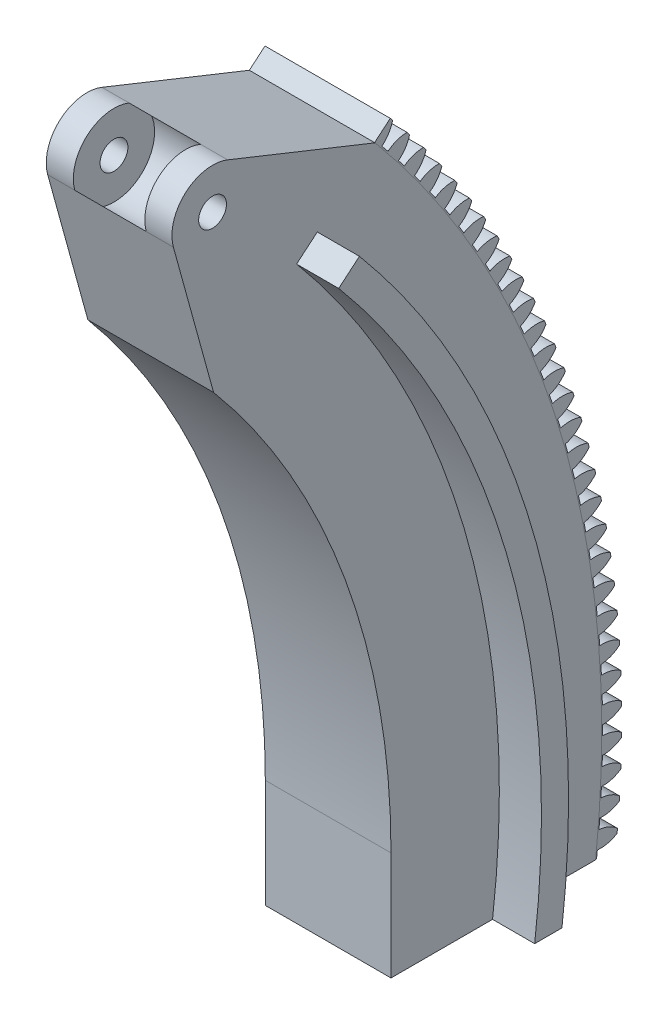
SolidWorks part; units mm, degrees
material "ABS"
ref_plane "Front Plane" through (0, 0, 0) normal (0, 0, 1) x (1, 0, 0)
ref_plane "Top Plane" through (0, 0, 0) normal (0, 1, 0) x (1, 0, 0)
ref_plane "Right Plane" through (0, 0, 0) normal (1, 0, 0) x (0, 0, -1)
ref_plane "Plane2" through (6.35, 0, 0) normal (1, 0, 0) x (0, 0, -1)
sketch "Sketch1" plane through (0, 0, 0) normal (1, 0, 0) x (0, 0, -1)
  line L0 (-1000, 0) -> (177.8, 0) construction
  line L1 (177.8, 0) -> (177.8, -25.4)
  line L2 (0, 0) -> (136.2027, 114.2876) construction
  line L4 (227.2, 0) -> (49000, 0) construction
  line L7 (177.8, -25.4) -> (227.2, -25.4) construction
  line L8 (227.2, 0) -> (227.2, -25.4) construction
  line L10 (-1.0719, -0.8495) -> (179.1555, 141.9904) construction
  line L61 (181.0098, 139.6187) -> (0, 0) construction
  line L62 (136.2027, 114.2876) -> (126.7844, 148.4774)
  line L64 (177.8, -25.4) -> (225.7757, -25.4)
  line L65 (136.2027, 114.2876) -> (155.124, 130.1645) construction
  line L66 (155.124, 130.1645) -> (174.0453, 146.0413) construction
  line L68 (0, 0) -> (35966.99, 34732.9185) construction
  line L69 (178.0587, 141.1212) -> (178.0836, 141.1409) construction
  line L70 (0, 0) -> (135.9673, 151.007) construction
  line L71 (139.5033, 159.8514) -> (174.0453, 146.0413)
  arc A2 (177.8, 0) -> (136.2027, 114.2876) centre (0, 0) ccw
  circle A19 centre (0, 0) radius 228.6 construction
  arc A22 (174.0453, 146.0413) -> (227.2, 0) centre (0, 0) cw
  arc A23 (227.2, 0) -> (225.7757, -25.4) centre (0, 0) cw
  arc A24 (126.7844, 148.4774) -> (139.5033, 159.8514) centre (135.9673, 151.007) cw
  point P6 (178.0836, 141.1409)
  point P7 (136.2027, 114.2876)
  dimension "D1" = 177.8
  dimension "D2" = 6.35
  dimension "D12" = 457.2
  dimension "D8" = 9.525
  dimension "D3" = 40
  dimension "D4" = 49.4
  dimension "D5" = 25.4
  dimension "D6" = 203.2
  dimension "D7" = 48
  dimension "D13" = 44
sketch "Sketch2" plane through (6.35, 0, 0) normal (1, 0, 0) x (0, 0, -1)
  line L0 (0, 0) -> (165.1, 0) construction
  line L1 (165.1, 0) -> (190.5, 0) construction
  line L2 (0, 0) -> (49240.3877, 8682.4089) construction
  circle A0 centre (165.1, 0) radius 3.2639
  circle A1 centre (190.5, 0) radius 3.2639
  arc A3 (165.1, 0) -> (162.5918, 28.6693) centre (0, 0) ccw construction
  circle A4 centre (162.5918, 28.6693) radius 3.2639
  arc A5 (190.5, 0) -> (187.6059, 33.08) centre (0, 0) ccw construction
  circle A6 centre (187.6059, 33.08) radius 3.2639
  dimension "D3" = 6.5278
  dimension "D4" = 6.5278
  dimension "D6" = 6.5278
  dimension "D7" = 6.5278
  dimension "D1" = 165.1
  dimension "D2" = 25.4
  dimension "D5" = 10
sketch "Sketch11" plane through (6.35, 0, 0) normal (1, 0, 0) x (0, 0, -1)
  line L0 (-785.502, -659.1144) -> (0, 0) construction
  line L2 (-1000, 0) -> (0, 0) construction
  line L4 (155.6602, 130.6144) -> (177.7223, 149.1267)
  line L5 (177.7223, 149.1267) -> (921.7047, 773.4021) construction
  line L6 (232, 0) -> (232, -25.4) construction
  line L7 (232, -25.4) -> (222.9391, -25.4) construction
  line L8 (201.6062, -25.4) -> (230.6054, -25.4)
  line L9 (203.2, 0) -> (232, 0) construction
  arc A0 (-230, 0) -> (-176.1902, -147.8412) centre (0, 0) ccw construction
  arc A1 (-232, 0) -> (-177.7223, -149.1267) centre (0, 0) ccw construction
  arc A2 (-229.6, 0) -> (-175.8838, -147.584) centre (0, 0) ccw construction
  arc A3 (232, 0) -> (177.7223, 149.1267) centre (0, 0) ccw
  arc A4 (230, 0) -> (176.1902, 147.8412) centre (0, 0) ccw construction
  arc A5 (-229.6, 0) -> (-175.8838, -147.584) centre (0, 0) ccw
  arc A6 (155.6602, 130.6144) -> (203.2, 0) centre (0, 0) cw
  arc A7 (232, 0) -> (230.6054, -25.4) centre (0, 0) cw
  arc A8 (203.2, 0) -> (201.6062, -25.4) centre (0, 0) cw
  dimension "D1" = 460
  dimension "D2" = 464
  dimension "D4" = 203.2
  dimension "D3" = 2.4
  dimension "D6" = 25.4
extrude "Boss-Extrude2" add sketch "Sketch11" against normal blind 6.35 contours A3 L4 region at (6.35, 60.7212, -203.0048)
sketch "Sketch12" plane through (6.35, 0, 0) normal (1, 0, 0) x (0, 0, -1)
  line L0 (0, 0) -> (232, 0) construction
  line L2 (229.9946, 1.5708) -> (229.9946, -1.5708) construction
  line L3 (0, 0) -> (227.4972, 1.1241) construction
  line L4 (225.6789, 0) -> (232.9848, 2.6591) construction
  line L5 (0, 0) -> (232.9783, 3.1825) construction
  line L6 (229.9946, 1.5708) -> (229.9517, 4.7121) construction
  circle A0 centre (0, 0) radius 230 construction
  arc A1 (230.6054, -25.4) -> (177.7223, 149.1267) centre (0, 0) ccw construction
  circle A2 centre (0, 0) radius 227.5 construction
  arc A3 (227.4972, 1.1241) -> (232.9725, 3.5819) centre (227.4606, 8.5329) ccw
  arc A4 (231.5994, -25.5095) -> (232.9725, -3.5819) centre (0, 0) cw construction
  arc A5 (227.4972, -1.1241) -> (232.9725, -3.5819) centre (227.4606, -8.5329) cw
  arc A6 (231.5994, -25.5095) -> (178.4884, 149.7695) centre (0, 0) ccw
  arc A7 (231.5994, -25.5095) -> (232.9725, 3.5819) centre (0, 0) ccw construction
  arc A8 (227.4972, 1.1241) -> (227.4972, -1.1241) centre (0, 0) cw
  arc A9 (230.6054, -25.4) -> (177.7223, 149.1267) centre (0, 0) ccw construction
  arc A10 (232.9725, 3.5819) -> (232.9725, -3.5819) centre (0, 0) cw
  dimension "D1" = 460
  dimension "D3" = 20
  dimension "D4" = 0.783
  dimension "D5" = 4.5
  dimension "D2" = 1
extrude "Boss-Extrude3" add sketch "Sketch1" along normal blind 29.464
extrude "Cut-Extrude4" cut sketch "Sketch12" against normal blind 6.35
pattern_circular "CirPattern3" count 230 every 1.565 about axis through (0, 0, 0) along (1, 0, 0) of "Cut-Extrude4"
sketch "Sketch15" plane through (6.35, 0, 0) normal (1, 0, 0) x (0, 0, -1)
  line L0 (0, 0) -> (135.9673, 151.007) construction
  line L2 (0, 0) -> (102.4673, 0) construction
  circle A0 centre (135.9673, 151.007) radius 3.2639
  dimension "D3" = 6.5278
  dimension "D1" = 203.2
  dimension "D2" = 48
extrude "Cut-Extrude7" cut sketch "Sketch15" against normal through all both and the other way through all
sketch "Sketch22" plane through (6.35, 0, 0) normal (1, 0, 0) x (0, 0, -1)
  line L0 (0, 0) -> (135.9673, 151.007)
  line L1 (0, 0) -> (177.8, 0)
  dimension "D1" = 177.8
sketch "Sketch23" plane through (0, 0, 0) normal (1, 0, 0) x (0, 0, -1)
  line L0 (0, 0) -> (177.8, 0) construction
  line L1 (0, 0) -> (136.2027, 114.2876) construction
  line L2 (177.8, 0) -> (196.85, 0) construction
  line L3 (136.2027, 114.2876) -> (155.6602, 130.6144) construction
  line L5 (155.6602, 130.6144) -> (160.5246, 134.6961)
  line L7 (201.6062, -25.4) -> (0, 0) construction
  line L8 (208.0049, -25.4) -> (201.6062, -25.4)
  line L9 (177.8, -25.4) -> (226.0776, -25.4) construction
  arc A0 (177.8, 0) -> (136.2027, 114.2876) centre (0, 0) ccw construction
  circle A2 centre (196.85, 0) radius 6.35 construction
  arc A3 (203.2, 0) -> (155.6602, 130.6144) centre (0, 0) ccw
  arc A4 (209.55, 0) -> (160.5246, 134.6961) centre (0, 0) ccw
  circle A5 centre (215.9, 0) radius 6.35 construction
  arc A6 (203.2, 0) -> (201.6062, -25.4) centre (0, 0) cw
  arc A7 (209.55, 0) -> (208.0049, -25.4) centre (0, 0) cw
  dimension "D4" = 6.35
  dimension "D5" = 12.7
  dimension "D6" = 12.7
  dimension "D1" = 177.8
  dimension "D2" = 40
  dimension "D3" = 19.05
extrude "Boss-Extrude4" add sketch "Sketch23" against normal blind 9.8742
ref_plane "Plane3" through (14.732, 0, 0) normal (1, 0, 0) x (0, 0, -1)
mirror "Mirror2" about plane through (14.732, 0, 0) normal (1, 0, 0) of "Boss-Extrude4"
sketch "Sketch27" plane through (6.35, 0, 0) normal (1, 0, 0) x (0, 0, -1)
  line L2 (177.7223, 149.1267) -> (174.0453, 146.0413)
  line L3 (177.7223, 149.1267) -> (174.0453, 146.0413)
  line L7 (225.7757, -25.4) -> (226.0776, -25.4)
  line L8 (225.7757, -25.4) -> (226.0776, -25.4)
  arc A4 (227.2191, 11.3011) -> (227.0964, 13.5458) centre (0, 0) ccw
  arc A95 (231.8253, 9.0012) -> (231.7841, 10.0069) centre (0, 0) ccw
  arc A111 (227.3816, 7.3377) -> (231.8253, 9.0012) centre (227.1427, 14.7428) ccw
  arc A112 (227.3816, 7.3377) -> (231.8253, 9.0012) centre (227.1427, 14.7428) ccw
  arc A113 (231.7841, 10.0069) -> (227.2191, 11.3011) centre (227.5872, 3.9012) ccw
  arc A114 (231.7841, 10.0069) -> (227.2191, 11.3011) centre (227.5872, 3.9012) ccw
  arc A139 (227.2191, 11.3011) -> (227.0964, 13.5458) centre (0, 0) ccw
  arc A141 (227.0964, 13.5458) -> (231.493, 15.3301) centre (226.6552, 20.9417) ccw
  arc A143 (227.0964, 13.5458) -> (231.493, 15.3301) centre (226.6552, 20.9417) ccw
  arc A145 (231.493, 15.3301) -> (231.4243, 16.3343) centre (0, 0) ccw
  arc A147 (231.493, 15.3301) -> (231.4243, 16.3343) centre (0, 0) ccw
  arc A149 (231.4243, 16.3343) -> (226.8257, 17.5033) centre (227.3957, 10.1163) ccw
  arc A151 (231.4243, 16.3343) -> (226.8257, 17.5033) centre (227.3957, 10.1163) ccw
  arc A153 (226.8257, 17.5033) -> (226.6416, 19.7439) centre (0, 0) ccw
  arc A155 (226.8257, 17.5033) -> (226.6416, 19.7439) centre (0, 0) ccw
  arc A157 (226.6416, 19.7439) -> (230.9878, 21.6476) centre (225.9986, 27.1249) ccw
  arc A159 (226.6416, 19.7439) -> (230.9878, 21.6476) centre (225.9986, 27.1249) ccw
  arc A161 (230.9878, 21.6476) -> (230.8918, 22.6495) centre (0, 0) ccw
  arc A163 (230.9878, 21.6476) -> (230.8918, 22.6495) centre (0, 0) ccw
  arc A165 (230.8918, 22.6495) -> (226.2629, 23.6925) centre (227.0345, 16.3238) ccw
  arc A167 (230.8918, 22.6495) -> (226.2629, 23.6925) centre (227.0345, 16.3238) ccw
  arc A169 (226.2629, 23.6925) -> (226.0178, 25.9272) centre (0, 0) ccw
  arc A171 (226.2629, 23.6925) -> (226.0178, 25.9272) centre (0, 0) ccw
  arc A173 (226.0178, 25.9272) -> (230.3104, 27.9489) centre (225.1734, 33.2879) ccw
  arc A175 (226.0178, 25.9272) -> (230.3104, 27.9489) centre (225.1734, 33.2879) ccw
  arc A177 (230.3104, 27.9489) -> (230.1869, 28.9478) centre (0, 0) ccw
  arc A179 (230.3104, 27.9489) -> (230.1869, 28.9478) centre (0, 0) ccw
  arc A181 (230.1869, 28.9478) -> (225.5314, 29.8639) centre (226.5039, 22.5191) ccw
  arc A182 (230.1869, 28.9478) -> (225.5314, 29.8639) centre (226.5039, 22.5191) ccw
  arc A184 (225.5314, 29.8639) -> (225.2252, 32.0911) centre (0, 0) ccw
  arc A186 (225.5314, 29.8639) -> (225.2252, 32.0911) centre (0, 0) ccw
  arc A189 (231.8253, 9.0012) -> (231.7841, 10.0069) centre (0, 0) ccw
  arc A282 (225.2252, 32.0911) -> (229.461, 34.2294) centre (224.1801, 39.426) ccw
  arc A284 (225.2252, 32.0911) -> (229.461, 34.2294) centre (224.1801, 39.426) ccw
  arc A286 (229.461, 34.2294) -> (229.3104, 35.2245) centre (0, 0) ccw
  arc A288 (229.461, 34.2294) -> (229.3104, 35.2245) centre (0, 0) ccw
  arc A290 (229.3104, 35.2245) -> (224.6315, 36.0131) centre (225.8043, 28.6976) ccw
  arc A292 (229.3104, 35.2245) -> (224.6315, 36.0131) centre (225.8043, 28.6976) ccw
  arc A294 (224.6315, 36.0131) -> (224.2647, 38.2311) centre (0, 0) ccw
  arc A296 (224.6315, 36.0131) -> (224.2647, 38.2311) centre (0, 0) ccw
  arc A298 (224.2647, 38.2311) -> (228.4404, 40.4843) centre (223.0196, 45.5347) ccw
  arc A300 (224.2647, 38.2311) -> (228.4404, 40.4843) centre (223.0196, 45.5347) ccw
  arc A302 (228.4404, 40.4843) -> (228.2626, 41.4749) centre (0, 0) ccw
  arc A304 (228.4404, 40.4843) -> (228.2626, 41.4749) centre (0, 0) ccw
  arc A306 (228.2626, 41.4749) -> (223.564, 42.1355) centre (224.9362, 34.8547) ccw
  arc A308 (228.2626, 41.4749) -> (223.564, 42.1355) centre (224.9362, 34.8547) ccw
  arc A310 (223.564, 42.1355) -> (223.1367, 44.3426) centre (0, 0) ccw
  arc A312 (223.564, 42.1355) -> (223.1367, 44.3426) centre (0, 0) ccw
  arc A314 (223.1367, 44.3426) -> (227.2494, 46.709) centre (221.6926, 51.6095) ccw
  arc A316 (223.1367, 44.3426) -> (227.2494, 46.709) centre (221.6926, 51.6095) ccw
  arc A318 (227.2494, 46.709) -> (227.0446, 47.6944) centre (0, 0) ccw
  arc A320 (227.2494, 46.709) -> (227.0446, 47.6944) centre (0, 0) ccw
  arc A322 (227.0446, 47.6944) -> (222.3296, 48.2264) centre (223.9002, 40.9858) ccw
  arc A324 (227.0446, 47.6944) -> (222.3296, 48.2264) centre (223.9002, 40.9858) ccw
  arc A326 (222.3296, 48.2264) -> (221.8422, 50.421) centre (0, 0) ccw
  arc A328 (222.3296, 48.2264) -> (221.8422, 50.421) centre (0, 0) ccw
  arc A330 (221.8422, 50.421) -> (225.8887, 52.8988) centre (220.2002, 57.6457) ccw
  arc A332 (221.8422, 50.421) -> (225.8887, 52.8988) centre (220.2002, 57.6457) ccw
  arc A334 (225.8887, 52.8988) -> (225.6571, 53.8783) centre (0, 0) ccw
  arc A336 (225.8887, 52.8988) -> (225.6571, 53.8783) centre (0, 0) ccw
  arc A338 (225.6571, 53.8783) -> (220.9294, 54.2813) centre (222.6972, 47.0863) ccw
  arc A340 (225.6571, 53.8783) -> (220.9294, 54.2813) centre (222.6972, 47.0863) ccw
  arc A342 (220.9294, 54.2813) -> (220.3822, 56.4618) centre (0, 0) ccw
  arc A344 (220.9294, 54.2813) -> (220.3822, 56.4618) centre (0, 0) ccw
  arc A346 (220.3822, 56.4618) -> (224.3595, 59.0492) centre (218.5434, 63.6389) ccw
  arc A348 (220.3822, 56.4618) -> (224.3595, 59.0492) centre (218.5434, 63.6389) ccw
  arc A350 (224.3595, 59.0492) -> (224.1012, 60.022) centre (0, 0) ccw
  arc A352 (224.3595, 59.0492) -> (224.1012, 60.022) centre (0, 0) ccw
  arc A354 (224.1012, 60.022) -> (219.3643, 60.2956) centre (221.3279, 53.1516) ccw
  arc A356 (224.1012, 60.022) -> (219.3643, 60.2956) centre (221.3279, 53.1516) ccw
  arc A358 (219.3643, 60.2956) -> (218.7577, 62.4604) centre (0, 0) ccw
  arc A360 (219.3643, 60.2956) -> (218.7577, 62.4604) centre (0, 0) ccw
  arc A362 (218.7577, 62.4604) -> (222.6629, 65.1555) centre (216.7236, 69.5847) ccw
  arc A364 (218.7577, 62.4604) -> (222.6629, 65.1555) centre (216.7236, 69.5847) ccw
  arc A366 (222.6629, 65.1555) -> (222.3781, 66.1209) centre (0, 0) ccw
  arc A368 (222.6629, 65.1555) -> (222.3781, 66.1209) centre (0, 0) ccw
  arc A370 (222.3781, 66.1209) -> (217.6355, 66.265) centre (219.7935, 59.1773) ccw
  arc A372 (222.3781, 66.1209) -> (217.6355, 66.265) centre (219.7935, 59.1773) ccw
  arc A374 (217.6355, 66.265) -> (216.97, 68.4124) centre (0, 0) ccw
  arc A376 (217.6355, 66.265) -> (216.97, 68.4124) centre (0, 0) ccw
  arc A378 (216.97, 68.4124) -> (220.8001, 71.2132) centre (214.742, 75.4785) ccw
  arc A380 (216.97, 68.4124) -> (220.8001, 71.2132) centre (214.742, 75.4785) ccw
  arc A382 (220.8001, 71.2132) -> (220.4891, 72.1704) centre (0, 0) ccw
  arc A384 (220.8001, 71.2132) -> (220.4891, 72.1704) centre (0, 0) ccw
  arc A386 (220.4891, 72.1704) -> (215.7443, 72.185) centre (218.0951, 65.1589) ccw
  arc A388 (220.4891, 72.1704) -> (215.7443, 72.185) centre (218.0951, 65.1589) ccw
  arc A390 (215.7443, 72.185) -> (215.0204, 74.3134) centre (0, 0) ccw
  arc A394 (215.7443, 72.185) -> (215.0204, 74.3134) centre (0, 0) ccw
  arc A398 (215.0204, 74.3134) -> (218.7726, 77.2177) centre (212.6002, 81.3159) ccw
  arc A402 (215.0204, 74.3134) -> (218.7726, 77.2177) centre (212.6002, 81.3159) ccw
  arc A406 (218.7726, 77.2177) -> (218.4355, 78.1661) centre (0, 0) ccw
  arc A410 (218.7726, 77.2177) -> (218.4355, 78.1661) centre (0, 0) ccw
  arc A414 (218.4355, 78.1661) -> (213.692, 78.0511) centre (216.2339, 71.0918) ccw
  arc A418 (218.4355, 78.1661) -> (213.692, 78.0511) centre (216.2339, 71.0918) ccw
  arc A420 (213.692, 78.0511) -> (212.9103, 80.1589) centre (0, 0) ccw
  arc A422 (213.692, 78.0511) -> (212.9103, 80.1589) centre (0, 0) ccw
  arc A423 (212.9103, 80.1589) -> (216.5817, 83.1646) centre (210.2998, 87.0927) ccw
  arc A424 (212.9103, 80.1589) -> (216.5817, 83.1646) centre (210.2998, 87.0927) ccw
  arc A425 (216.5817, 83.1646) -> (216.2189, 84.1034) centre (0, 0) ccw
  arc A426 (216.5817, 83.1646) -> (216.2189, 84.1034) centre (0, 0) ccw
  arc A427 (216.2189, 84.1034) -> (211.4804, 83.8589) centre (214.2114, 76.9716) ccw
  arc A428 (216.2189, 84.1034) -> (211.4804, 83.8589) centre (214.2114, 76.9716) ccw
  arc A429 (211.4804, 83.8589) -> (210.6414, 85.9446) centre (0, 0) ccw
  arc A430 (211.4804, 83.8589) -> (210.6414, 85.9446) centre (0, 0) ccw
  arc A431 (210.6414, 85.9446) -> (214.2293, 89.0495) centre (207.8424, 92.8045) ccw
  arc A432 (210.6414, 85.9446) -> (214.2293, 89.0495) centre (207.8424, 92.8045) ccw
  arc A434 (214.2293, 89.0495) -> (213.841, 89.978) centre (0, 0) ccw
  arc A436 (214.2293, 89.0495) -> (213.841, 89.978) centre (0, 0) ccw
  arc A438 (213.841, 89.978) -> (209.1109, 89.6041) centre (212.029, 82.794) ccw
  arc A440 (213.841, 89.978) -> (209.1109, 89.6041) centre (212.029, 82.794) ccw
  arc A442 (209.1109, 89.6041) -> (208.2152, 91.6661) centre (0, 0) ccw
  arc A444 (209.1109, 89.6041) -> (208.2152, 91.6661) centre (0, 0) ccw
  arc A446 (208.2152, 91.6661) -> (211.717, 94.8679) centre (205.2299, 98.4471) ccw
  arc A448 (208.2152, 91.6661) -> (211.717, 94.8679) centre (205.2299, 98.4471) ccw
  arc A450 (211.717, 94.8679) -> (211.3034, 95.7855) centre (0, 0) ccw
  arc A452 (211.717, 94.8679) -> (211.3034, 95.7855) centre (0, 0) ccw
  arc A454 (211.3034, 95.7855) -> (206.5853, 95.2825) centre (209.6884, 88.5547) ccw
  arc A456 (211.3034, 95.7855) -> (206.5853, 95.2825) centre (209.6884, 88.5547) ccw
  arc A458 (206.5853, 95.2825) -> (205.6337, 97.3193) centre (0, 0) ccw
  arc A460 (206.5853, 95.2825) -> (205.6337, 97.3193) centre (0, 0) ccw
  arc A462 (205.6337, 97.3193) -> (209.0467, 100.6155) centre (202.4643, 104.0162) ccw
  arc A464 (205.6337, 97.3193) -> (209.0467, 100.6155) centre (202.4643, 104.0162) ccw
  arc A466 (209.0467, 100.6155) -> (208.6082, 101.5215) centre (0, 0) ccw
  arc A467 (209.0467, 100.6155) -> (208.6082, 101.5215) centre (0, 0) ccw
  arc A468 (208.6082, 101.5215) -> (203.9056, 100.8898) centre (207.1913, 94.2492) ccw
  arc A469 (208.6082, 101.5215) -> (203.9056, 100.8898) centre (207.1913, 94.2492) ccw
  arc A470 (203.9056, 100.8898) -> (202.8987, 102.8998) centre (0, 0) ccw
  arc A471 (203.9056, 100.8898) -> (202.8987, 102.8998) centre (0, 0) ccw
  arc A472 (202.8987, 102.8998) -> (206.2204, 106.288) centre (199.5476, 109.5076) ccw
  arc A473 (202.8987, 102.8998) -> (206.2204, 106.288) centre (199.5476, 109.5076) ccw
  arc A474 (206.2204, 106.288) -> (205.7574, 107.1817) centre (0, 0) ccw
  arc A475 (206.2204, 106.288) -> (205.7574, 107.1817) centre (0, 0) ccw
  arc A476 (205.7574, 107.1817) -> (201.0737, 106.4218) centre (204.5396, 99.8735) ccw
  arc A477 (205.7574, 107.1817) -> (201.0737, 106.4218) centre (204.5396, 99.8735) ccw
  arc A478 (201.0737, 106.4218) -> (200.0123, 108.4036) centre (0, 0) ccw
  arc A479 (201.0737, 106.4218) -> (200.0123, 108.4036) centre (0, 0) ccw
  arc A480 (200.0123, 108.4036) -> (203.2402, 111.8812) centre (196.4819, 114.9174) ccw
  arc A481 (200.0123, 108.4036) -> (203.2402, 111.8812) centre (196.4819, 114.9174) ccw
  arc A482 (203.2402, 111.8812) -> (202.7529, 112.7619) centre (0, 0) ccw
  arc A483 (203.2402, 111.8812) -> (202.7529, 112.7619) centre (0, 0) ccw
  arc A484 (202.7529, 112.7619) -> (198.0918, 111.8744) centre (201.7352, 105.4232) ccw
  arc A485 (202.7529, 112.7619) -> (198.0918, 111.8744) centre (201.7352, 105.4232) ccw
  arc A486 (198.0918, 111.8744) -> (196.9766, 113.8264) centre (0, 0) ccw
  arc A487 (198.0918, 111.8744) -> (196.9766, 113.8264) centre (0, 0) ccw
  arc A488 (196.9766, 113.8264) -> (200.1084, 117.3909) centre (193.2697, 120.2413) ccw
  arc A489 (196.9766, 113.8264) -> (200.1084, 117.3909) centre (193.2697, 120.2413) ccw
  arc A490 (200.1084, 117.3909) -> (199.5972, 118.258) centre (0, 0) ccw
  arc A491 (200.1084, 117.3909) -> (199.5972, 118.258) centre (0, 0) ccw
  arc A492 (199.5972, 118.258) -> (194.9621, 117.2435) centre (198.7804, 110.8942) ccw
  arc A493 (199.5972, 118.258) -> (194.9621, 117.2435) centre (198.7804, 110.8942) ccw
  arc A494 (194.9621, 117.2435) -> (193.794, 119.1643) centre (0, 0) ccw
  arc A495 (194.9621, 117.2435) -> (193.794, 119.1643) centre (0, 0) ccw
  arc A496 (193.794, 119.1643) -> (196.8272, 122.8131) centre (189.9132, 125.4756) ccw
  arc A497 (193.794, 119.1643) -> (196.8272, 122.8131) centre (189.9132, 125.4756) ccw
  arc A498 (196.8272, 122.8131) -> (196.2926, 123.6658) centre (0, 0) ccw
  arc A499 (196.8272, 122.8131) -> (196.2926, 123.6658) centre (0, 0) ccw
  arc A500 (196.2926, 123.6658) -> (191.6869, 122.5251) centre (195.6771, 116.2824) ccw
  arc A501 (196.2926, 123.6658) -> (191.6869, 122.5251) centre (195.6771, 116.2824) ccw
  arc A502 (191.6869, 122.5251) -> (190.4667, 124.4133) centre (0, 0) ccw
  arc A503 (191.6869, 122.5251) -> (190.4667, 124.4133) centre (0, 0) ccw
  arc A504 (190.4667, 124.4133) -> (193.3992, 128.1435) centre (186.415, 130.6162) ccw
  arc A505 (190.4667, 124.4133) -> (193.3992, 128.1435) centre (186.415, 130.6162) ccw
  arc A506 (193.3992, 128.1435) -> (192.8414, 128.9814) centre (0, 0) ccw
  arc A507 (193.3992, 128.1435) -> (192.8414, 128.9814) centre (0, 0) ccw
  arc A508 (192.8414, 128.9814) -> (188.2686, 127.7153) centre (192.4279, 121.5839) ccw
  arc A509 (192.8414, 128.9814) -> (188.2686, 127.7153) centre (192.4279, 121.5839) ccw
  arc A510 (188.2686, 127.7153) -> (186.9974, 129.5694) centre (0, 0) ccw
  arc A511 (188.2686, 127.7153) -> (186.9974, 129.5694) centre (0, 0) ccw
  arc A512 (186.9974, 129.5694) -> (189.8268, 133.3784) centre (182.7777, 135.6594) ccw
  arc A513 (186.9974, 129.5694) -> (189.8268, 133.3784) centre (182.7777, 135.6594) ccw
  arc A514 (189.8268, 133.3784) -> (189.2464, 134.2007) centre (0, 0) ccw
  arc A515 (189.8268, 133.3784) -> (189.2464, 134.2007) centre (0, 0) ccw
  arc A516 (189.2464, 134.2007) -> (184.7098, 132.8101) centre (189.0351, 126.7947) ccw
  arc A517 (189.2464, 134.2007) -> (184.7098, 132.8101) centre (189.0351, 126.7947) ccw
  arc A518 (184.7098, 132.8101) -> (183.3884, 134.6289) centre (0, 0) ccw
  arc A519 (184.7098, 132.8101) -> (183.3884, 134.6289) centre (0, 0) ccw
  arc A520 (225.7757, -25.4) -> (174.0453, 146.0413) centre (0, 0) ccw
  arc A521 (225.7757, -25.4) -> (174.0453, 146.0413) centre (0, 0) ccw
  arc A522 (227.4972, -1.1241) -> (227.4972, 1.1241) centre (0, 0) ccw
  arc A523 (227.4972, -1.1241) -> (227.4972, 1.1241) centre (0, 0) ccw
  arc A524 (227.4972, 1.1241) -> (231.9847, 2.6656) centre (227.4606, 8.5329) ccw
  arc A525 (227.4972, 1.1241) -> (231.9847, 2.6656) centre (227.4606, 8.5329) ccw
  arc A526 (231.9847, 2.6656) -> (231.9709, 3.672) centre (0, 0) ccw
  arc A527 (231.9847, 2.6656) -> (231.9709, 3.672) centre (0, 0) ccw
  arc A528 (231.9709, 3.672) -> (227.4431, 5.0904) centre (227.6088, -2.3167) ccw
  arc A529 (231.9709, 3.672) -> (227.4431, 5.0904) centre (227.6088, -2.3167) ccw
  arc A530 (227.4431, 5.0904) -> (227.3816, 7.3377) centre (0, 0) ccw
  arc A531 (227.4431, 5.0904) -> (227.3816, 7.3377) centre (0, 0) ccw
  arc A532 (231.9709, -3.672) -> (231.9847, -2.6656) centre (0, 0) ccw
  arc A533 (231.9709, -3.672) -> (231.9847, -2.6656) centre (0, 0) ccw
  arc A534 (231.9847, -2.6656) -> (227.4972, -1.1241) centre (227.4606, -8.5329) ccw
  arc A535 (231.9847, -2.6656) -> (227.4972, -1.1241) centre (227.4606, -8.5329) ccw
  arc A536 (183.3884, 134.6289) -> (186.1128, 138.5137) centre (179.004, 140.6013) ccw
  arc A537 (183.3884, 134.6289) -> (186.1128, 138.5137) centre (179.004, 140.6013) ccw
  arc A538 (186.1128, 138.5137) -> (185.5101, 139.3198) centre (0, 0) ccw
  arc A539 (186.1128, 138.5137) -> (185.5101, 139.3198) centre (0, 0) ccw
  arc A540 (185.5101, 139.3198) -> (181.0132, 137.8059) centre (185.5011, 131.9108) ccw
  arc A541 (185.5101, 139.3198) -> (181.0132, 137.8059) centre (185.5011, 131.9108) ccw
  arc A542 (181.0132, 137.8059) -> (179.6426, 139.5879) centre (0, 0) ccw
  arc A543 (181.0132, 137.8059) -> (179.6426, 139.5879) centre (0, 0) ccw
  arc A544 (179.6426, 139.5879) -> (182.2598, 143.5456) centre (175.0967, 145.4383) ccw
  arc A545 (179.6426, 139.5879) -> (182.2598, 143.5456) centre (175.0967, 145.4383) ccw
  arc A546 (182.2598, 143.5456) -> (181.6354, 144.335) centre (0, 0) ccw
  arc A547 (182.2598, 143.5456) -> (181.6354, 144.335) centre (0, 0) ccw
  arc A548 (181.6354, 144.335) -> (177.1815, 142.6988) centre (181.8288, 136.9286) ccw
  arc A549 (181.6354, 144.335) -> (177.1815, 142.6988) centre (181.8288, 136.9286) ccw
  arc A550 (177.1815, 142.6988) -> (175.7628, 144.4427) centre (0, 0) ccw
  arc A551 (177.1815, 142.6988) -> (175.7628, 144.4427) centre (0, 0) ccw
  arc A552 (175.7628, 144.4427) -> (178.2709, 148.4705) centre (171.0587, 150.1668) ccw
  arc A553 (175.7628, 144.4427) -> (178.2709, 148.4705) centre (171.0587, 150.1668) ccw
  arc A554 (178.2709, 148.4705) -> (177.7223, 149.1267) centre (0, 0) ccw
  arc A555 (178.2709, 148.4705) -> (177.7223, 149.1267) centre (0, 0) ccw
  arc A556 (226.0776, -25.4) -> (226.2629, -23.6925) centre (0, 0) ccw
  arc A557 (226.0776, -25.4) -> (226.2629, -23.6925) centre (0, 0) ccw
  arc A558 (226.2629, -23.6925) -> (230.8918, -22.6495) centre (227.0345, -16.3238) ccw
  arc A559 (226.2629, -23.6925) -> (230.8918, -22.6495) centre (227.0345, -16.3238) ccw
  arc A560 (230.8918, -22.6495) -> (230.9878, -21.6476) centre (0, 0) ccw
  arc A561 (230.8918, -22.6495) -> (230.9878, -21.6476) centre (0, 0) ccw
  arc A562 (230.9878, -21.6476) -> (226.6416, -19.7439) centre (225.9986, -27.1249) ccw
  arc A563 (230.9878, -21.6476) -> (226.6416, -19.7439) centre (225.9986, -27.1249) ccw
  arc A564 (226.6416, -19.7439) -> (226.8257, -17.5033) centre (0, 0) ccw
  arc A565 (226.6416, -19.7439) -> (226.8257, -17.5033) centre (0, 0) ccw
  arc A566 (226.8257, -17.5033) -> (231.4243, -16.3343) centre (227.3957, -10.1163) ccw
  arc A567 (226.8257, -17.5033) -> (231.4243, -16.3343) centre (227.3957, -10.1163) ccw
  arc A568 (231.4243, -16.3343) -> (231.493, -15.3301) centre (0, 0) ccw
  arc A569 (231.4243, -16.3343) -> (231.493, -15.3301) centre (0, 0) ccw
  arc A570 (231.493, -15.3301) -> (227.0964, -13.5458) centre (226.6552, -20.9417) ccw
  arc A571 (231.493, -15.3301) -> (227.0964, -13.5458) centre (226.6552, -20.9417) ccw
  arc A572 (227.0964, -13.5458) -> (227.2191, -11.3011) centre (0, 0) ccw
  arc A573 (227.0964, -13.5458) -> (227.2191, -11.3011) centre (0, 0) ccw
  arc A574 (227.2191, -11.3011) -> (231.7841, -10.0069) centre (227.5872, -3.9012) ccw
  arc A575 (227.2191, -11.3011) -> (231.7841, -10.0069) centre (227.5872, -3.9012) ccw
  arc A576 (231.7841, -10.0069) -> (231.8253, -9.0012) centre (0, 0) ccw
  arc A577 (231.7841, -10.0069) -> (231.8253, -9.0012) centre (0, 0) ccw
  arc A578 (231.8253, -9.0012) -> (227.3816, -7.3377) centre (227.1427, -14.7428) ccw
  arc A579 (231.8253, -9.0012) -> (227.3816, -7.3377) centre (227.1427, -14.7428) ccw
  arc A580 (227.3816, -7.3377) -> (227.4431, -5.0904) centre (0, 0) ccw
  arc A581 (227.3816, -7.3377) -> (227.4431, -5.0904) centre (0, 0) ccw
  arc A582 (227.4431, -5.0904) -> (231.9709, -3.672) centre (227.6088, 2.3167) ccw
  arc A583 (227.4431, -5.0904) -> (231.9709, -3.672) centre (227.6088, 2.3167) ccw
  dimension "D1" = 0
extrude "Boss-Extrude6" add sketch "Sketch27" along normal blind 23.0187
ref_plane "Plane4" through (6.35, 0, 0) normal (-1, 0, 0) x (0, 0, 1)
sketch "Sketch28" plane through (6.35, 0, 0) normal (1, 0, 0) x (0, 0, -1)
  circle A0 centre (135.9673, 151.007) radius 9.525
  arc A1 (139.5033, 159.8514) -> (126.7844, 148.4774) centre (135.9673, 151.007) ccw construction
extrude "Cut-Extrude8" cut sketch "Sketch28" along normal blind 16.764
sketch "Sketch29" plane through (0, -25.4, 0) normal (0, -1, 0) x (1, 0, 0)
  line L0 (14.6844, -226.0776) -> (14.732, -177.8) construction
  line L1 (29.3687, -226.0776) -> (0, -226.0776) construction
  line L2 (29.464, -177.8) -> (0, -177.8) construction
  circle A0 centre (14.7082, -201.9388) radius 3.175
  dimension "D1" = 6.35
extrude "Cut-Extrude9" cut sketch "Sketch29" against normal blind 12.7
equation "\"Module\"= 2mm"
equation "\"Number of Teeth\"= 230"
equation "\"D1@Sketch12\"=\"Module\" * \"Number of Teeth\""
equation "\"D4@Sketch12\"=180 / \"Number of Teeth\""
equation "\"D2\"= 360 / \"Number of Teeth\""
equation "\"D2@Sketch11\"=( \"Number of Teeth\" + 2) * \"Module\""
equation "\"D2@CirPattern3\"= 360 / \"Number of Teeth\""
equation "\"D5@Sketch12\"= 2.25 * \"Module\""
equation "\"D1@CirPattern3\"=\"Number of Teeth\""
